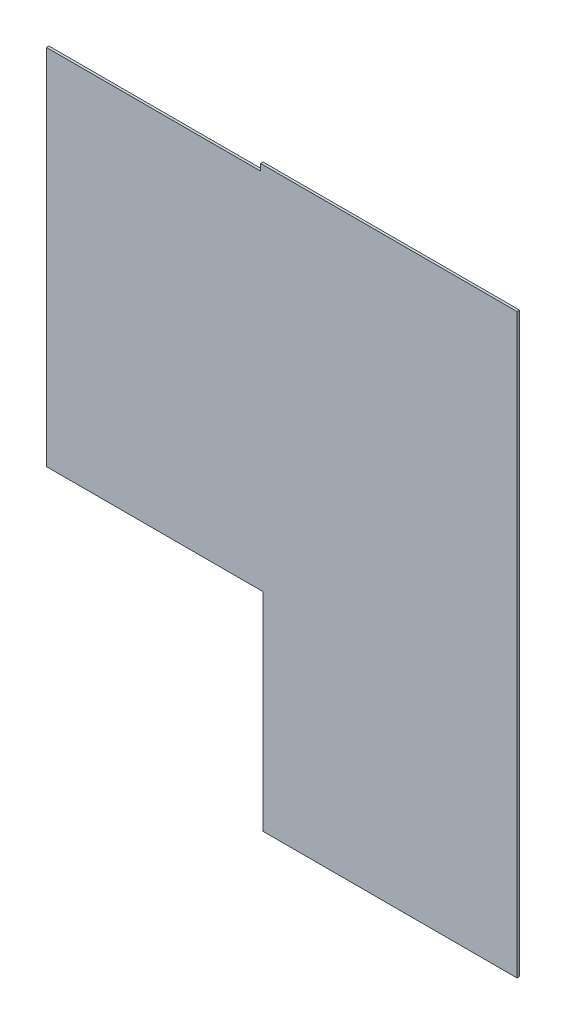
SolidWorks part; units mm, degrees
ref_plane "Спереди" through (0, 0, 0) normal (0, 0, 1) x (1, 0, 0)
ref_plane "Сверху" through (0, 0, 0) normal (0, 1, 0) x (1, 0, 0)
ref_plane "Справа" through (0, 0, 0) normal (1, 0, 0) x (0, 0, -1)
sketch "Эскиз2" plane through (0, 0, 0) normal (0, 0, 1) x (1, 0, 0)
  line L1 (1138.3, -949) -> (524, -949)
  line L2 (0, -447) -> (0, 431)
  line L3 (0, 431) -> (518, 431)
  line L4 (518, 431) -> (518, 447)
  line L5 (518, 447) -> (1138.3, 447)
  line L6 (1138.3, 447) -> (1138.3, -949)
  line L7 (0, -447) -> (524, -447)
  line L8 (524, -447) -> (524, -949)
extrude "Бобышка-Вытянуть1" add sketch "Эскиз2" against normal blind 6
equation "\"Ширина груза\"= 420"
equation "\"Глубина груза\"= 490"
equation "\"Высота груза\"= 297"
equation "\"Ширина ячейки\"= \"Ширина груза\" + 10"
equation "\"Глубина ячейки\"= \"Глубина груза\" + 10"
equation "\"Высота ячейки\"= \"Высота груза\" + 10 + 13"
equation "\"Колво ячеек ширина\"= 2"
equation "\"Колво ячеек высота\"= 2"
equation "\"Толщина стенки\" = 6"
equation "\"Крепление дверцы\"= 5 "
equation "\"Ширина рейки\"= \"Толщина шестерни\""
equation "\"Высота рейки\"= 20"
equation "\"Высота пола\"= \"Толщина стенки\" * 2"
equation "\"Колво полозьев\"= 5"
equation "\"Отступ рейки\"= 20"
equation "\"Глубина каретки\"= \"Глубина ячейки\" + 30 + \"Мотор Y высота корпуса\" + 20"
equation "\"Длинна рейки\"= ( \"Ширина ячейки\" + \"Толщина стенки\" + \"Крепление дверцы\" ) * \"Колво ячеек ширина\" + \"Ширина ячейки выгрузки\" * \"Колво выгрузки\" + \"Толщина стенки\""
equation "\"Отступ шпильки\"= 26"
equation "\"Диаметр шпильки\"= 5"
equation "\"Длинна шпильки\"= ( \"Высота ячейки\" + \"Толщина стенки\" + \"Высота пола\" ) * \"Колво ячеек высота\" + ( \"Толщина стенки\" + \"Отступ рейки\" ) * 2 "
equation "\"Ширина пластины\"= 50  "
equation "\"Высота зона выгрузки\"= \"Высота ячейки\" * 2 + \"Толщина стенки\" * 2"
equation "\"Колво выгрузки\"= 1"
equation "\"Ширина ячейки выгрузки\"= \"Ширина ячейки\" + \"Толщина стенки\" + \"Отступ крепления мотора фиксации\"*2"
equation "\"Отступ крепления мотора фиксации\" = 30"
equation "\"Мотор X ширина корпуса\"= 42.3"
equation "\"Мотор X высота корпуса\"= 42.3"
equation "\"Мотор X длина корпуса\"= 40"
equation "\"Мотор X вылет вала\"= 19.8"
equation "\"Мотор Y ширина корпуса\"= 42.3"
equation "\"Мотор Y высота корпуса\"= 42.3"
equation "\"Мотор Y длина корпуса\"= 48"
equation "\"Мотор Y вылет вала\"= 30"
equation "\"Мотор Z ширина корпуса\"= 42"
equation "\"Мотор Z высота корпуса\"= 42"
equation "\"Мотор Z длина корпуса\"= 40"
equation "\"Мотор Z вылет вала\"= 23"
equation "\"Мотор диаметр вала ПРЕДВ\"= 5"
equation "\"Мотор шаг крепления ПРЕДВ\"= 31"
equation "\"Мотор диаметр отверстий ПРЕДВ\"= 3"
equation "\"Мотор глубина отверстий ПРЕДВ\"= 4.5"
equation "\"Мотор диаметр буртика ПРЕДВ\"= 22"
equation "\"Мотор высота буртика ПРЕДВ\"= 2"
equation "\"Мотор диаметр шкива ПРЕДВ\"= 16"
equation "\"Мотор длина шкива ПРЕДВ\"= 12"
equation "\"Мотор отступ шкива ПРЕДВ\"= 5"
equation "\"Мотор X шаг градусов\"= 1.8"
equation "\"Мотор Y шаг градусов\"= 1.8"
equation "\"Мотор Z шаг градусов\"= 1.8"
equation "\"Мотор Y диаметр ротора\"= 25.78"
equation "\"Толщина шестерни\"= 10"
equation "\"D1@Бобышка-Вытянуть1\"=\"Толщина стенки\""
